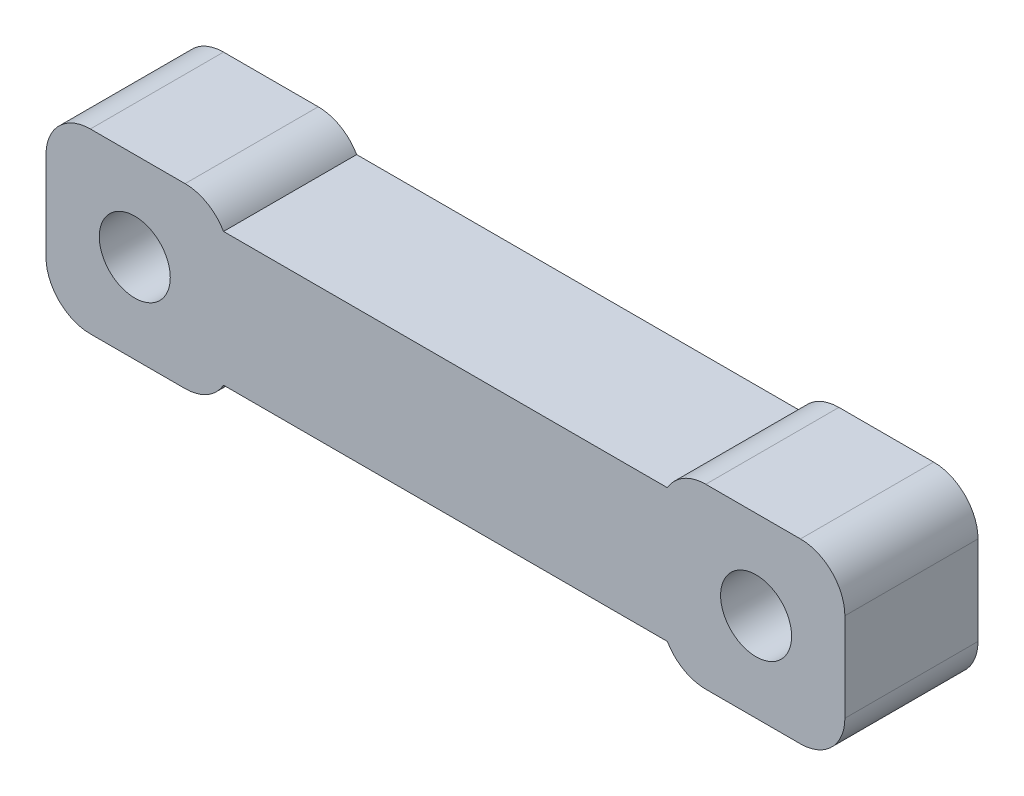
SolidWorks part; units mm, degrees
ref_plane "Front Plane" through (0, 0, 0) normal (0, 0, 1) x (1, 0, 0)
ref_plane "Top Plane" through (0, 0, 0) normal (0, 1, 0) x (1, 0, 0)
ref_plane "Right Plane" through (0, 0, 0) normal (1, 0, 0) x (0, 0, -1)
sketch "Sketch1" plane through (0, 0, 0) normal (0, 0, 1) x (1, 0, 0)
  line L0 (-7, 0) -> (7, 0) construction
  line L1 (9, -2) -> (-9, -2)
  line L2 (9, -2) -> (9, 2)
  line L3 (9, 2) -> (-9, 2)
  line L4 (-9, -2) -> (-9, 2)
  line L5 (9, -2) -> (-9, 2) construction
  line L6 (9, 2) -> (-9, -2) construction
  line L8 (-5, 2) -> (5, 2)
  line L9 (-5, 2) -> (-5, 1.5)
  line L10 (-5, 1.5) -> (5, 1.5)
  line L11 (5, 2) -> (5, 1.5)
  line L12 (-5, -2) -> (5, -2)
  line L13 (-5, -2) -> (-5, -1.5)
  line L14 (-5, -1.5) -> (5, -1.5)
  line L15 (5, -2) -> (5, -1.5)
  circle A0 centre (7, 0) radius 0.8
  circle A1 centre (-7, 0) radius 0.8
  point P0 (0, 0)
  dimension "D1" = 1.6
  dimension "D2" = 1.6
  dimension "D3" = 4
  dimension "D4" = 14
  dimension "D5" = 18
  dimension "D6" = 0.5
  dimension "D7" = 0.5
  dimension "D8" = 10
  dimension "D9" = 10
  dimension "D10" = 5
  dimension "D11" = 5
extrude "Boss-Extrude1" add sketch "Sketch1" along normal blind 3 contours L15 L1 L2 L3 L11 L10 L9 L4 L13 L14 A1 A0 region at (0, 0, 0)
fillet "Fillet1" radius 1 8 edges at (5, -2, 1.5) (9, -2, 1.5) (9, 2, 1.5) (5, 2, 1.5) (-5, -2, 1.5) (-5, 2, 1.5) (-9, -2, 1.5) (-9, 2, 1.5)
